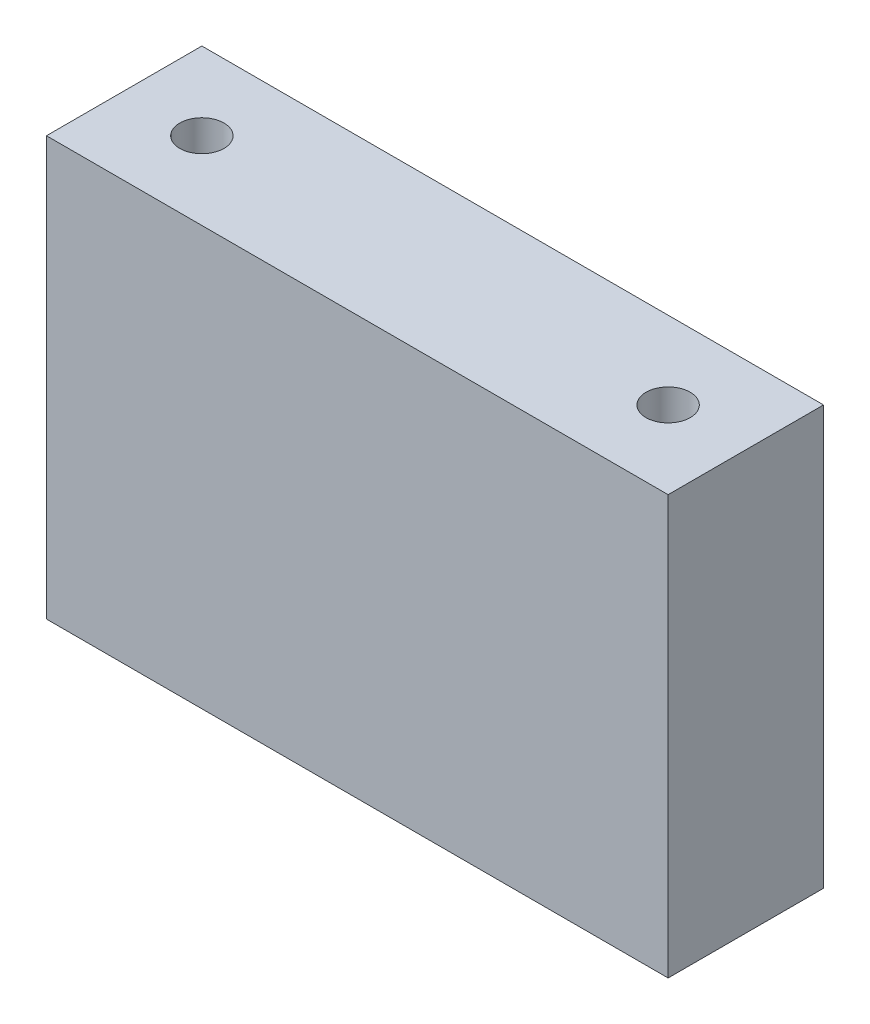
SolidWorks part; units mm, degrees
ref_plane "Front Plane" through (0, 0, 0) normal (0, 0, 1) x (1, 0, 0)
ref_plane "Top Plane" through (0, 0, 0) normal (0, 1, 0) x (1, 0, 0)
ref_plane "Right Plane" through (0, 0, 0) normal (1, 0, 0) x (0, 0, -1)
sketch "Sketch1" plane through (0, 0, 0) normal (0, 0, 1) x (1, 0, 0)
  line L1 (-19.05, 12.827) -> (19.05, 12.827)
  line L2 (-19.05, 12.827) -> (-19.05, -12.827)
  line L3 (-19.05, -12.827) -> (19.05, -12.827)
  line L4 (19.05, 12.827) -> (19.05, -12.827)
  line L5 (-19.05, 12.827) -> (19.05, -12.827) construction
  line L6 (-19.05, -12.827) -> (19.05, 12.827) construction
  point P0 (0, 0)
  dimension "D1" = 25.654
  dimension "D2" = 38.1
extrude "Boss-Extrude1" add sketch "Sketch1" along normal blind 9.525
sketch "Sketch2" plane through (0, 12.827, 0) normal (0, 1, 0) x (1, 0, 0)
  line L0 (-19.05, -9.525) -> (-19.05, 0) construction
  line L1 (19.05, -9.525) -> (19.05, 0) construction
  circle A0 centre (-14.2875, -4.7625) radius 2.54
  circle A1 centre (14.2875, -4.7625) radius 2.54
  point P4 (0, 0)
  point P9 (-19.05, -4.7625)
  dimension "D1" = 5.08
  dimension "D2" = 4.7625
  dimension "D3" = 4.7625
hole_wizard "#6-32 Tapped Hole1" positions "Sketch3" profile "Sketch4" tap size "#6-32" standard "ANSI Inch"
sketch "Sketch3" plane through (0, 12.827, 0) normal (0, 1, 0) x (1, 0, 0)
  point P0 (-14.2875, -4.7625)
  point P3 (14.2875, -4.7625)
sketch "Sketch4" plane through (-14.2875, 12.827, 4.7625) normal (1, 0, 0) x (0, 0, 1)
  line L0 (0, 0) -> (0, 8.4327)
  line L1 (0, 8.4327) -> (1.3525, 7.62)
  line L2 (1.3525, 7.62) -> (1.3525, 0)
  line L5 (1.3525, 0) -> (0, 0)
  line L10 (0, 8.4327) -> (-1.3526, 7.62) construction
  line L11 (0, -6.35) -> (0, 107.95) construction
  dimension "Tap Drill Dia." = 2.7051
  dimension "Tap Drill Depth" = 7.62
  dimension "Drill Angle" = 118
cosmetic thread "Hole Thread1"
cosmetic thread "Hole Thread2"
hole_wizard "#6-32 Tapped Hole2" positions "Sketch5" profile "Sketch6" tap size "#6-32" standard "ANSI Inch"
sketch "Sketch5" plane through (0, -12.827, 0) normal (0, -1, 0) x (-1, 0, 0)
  point P0 (-14.2875, -4.7625)
  point P3 (14.2875, -4.7625)
sketch "Sketch6" plane through (14.2875, -12.827, 4.7625) normal (1, 0, 0) x (0, 0, -1)
  line L0 (0, 0) -> (0, 10.2005)
  line L1 (0, 10.2005) -> (1.3525, 9.3878)
  line L2 (1.3525, 9.3878) -> (1.3525, 0)
  line L5 (1.3525, 0) -> (0, 0)
  line L10 (0, 10.2005) -> (-1.3526, 9.3878) construction
  line L11 (0, -6.35) -> (0, 107.95) construction
  dimension "Tap Drill Dia." = 2.7051
  dimension "Tap Drill Depth" = 9.3878
  dimension "Drill Angle" = 118
cosmetic thread "Hole Thread3"
cosmetic thread "Hole Thread4"
